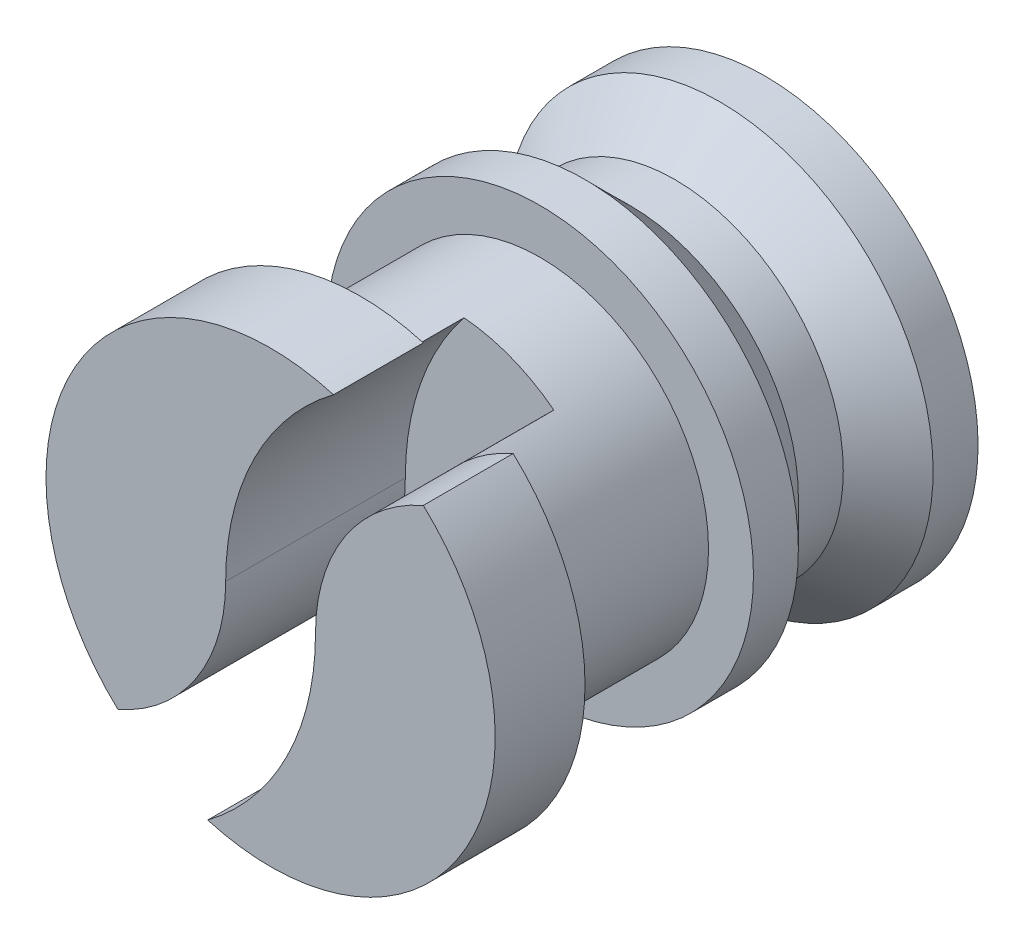
SolidWorks part; units mm, degrees
ref_plane "Спереди" through (0, 0, 0) normal (0, 0, 1) x (1, 0, 0)
ref_plane "Сверху" through (0, 0, 0) normal (0, 1, 0) x (1, 0, 0)
ref_plane "Справа" through (0, 0, 0) normal (1, 0, 0) x (0, 0, -1)
sketch "Эскиз1" plane through (0, 0, 0) normal (0, 0, 1) x (1, 0, 0)
  circle A0 centre (0, 0) radius 7.5
  dimension "D1" = 15
extrude "Бобышка-Вытянуть1" add sketch "Эскиз1" along normal blind 14 and the other way blind 2
sketch "Эскиз2" plane through (0, 0, 0) normal (0, 0, 1) x (1, 0, 0)
  circle A0 centre (0, 0) radius 9.5
  dimension "D1" = 19
extrude "Бобышка-Вытянуть2" add sketch "Эскиз2" along normal blind 2 from offset 2
sketch "Эскиз5" plane through (0, 0, 0) normal (0, 0, 1) x (1, 0, 0)
  circle A0 centre (0, 0) radius 10
  dimension "D1" = 20
extrude "Бобышка-Вытянуть3" add sketch "Эскиз5" along normal blind 4 from offset 12
sketch "Эскиз9" plane through (0, 0, 0) normal (0, 0, 1) x (1, 0, 0)
  line L0 (0, -1000) -> (0, 49000) construction
  line L1 (2, -999.8394) -> (2, 49000.1606) construction
  line L2 (-2, -1000.2983) -> (-2, 48999.7017) construction
  line L3 (-1000, 0) -> (49000, 0) construction
  circle A9 centre (0, 0) radius 15
  arc A10 (9.05, 11.9623) -> (-2, 0) centre (10, 0) ccw
  arc A11 (13.05, 7.3958) -> (2, 0) centre (10, 0) ccw
  arc A12 (-13.05, -7.3958) -> (-2, 0) centre (-10, 0) ccw
  arc A13 (-9.05, -11.9623) -> (2, 0) centre (-10, 0) ccw
  dimension "D1" = 30
  dimension "D5" = 10
  dimension "D2" = 2
  dimension "D3" = 2
extrude "Вырез-Вытянуть3" cut sketch "Эскиз9" along normal blind 8 from offset 8 contours A9 A13 A11 A10 A12 region at (0, 0, 0)
sketch "Эскиз10" plane through (0, 0, 0) normal (0, 0, 1) x (1, 0, 0)
  circle A0 centre (0, 0) radius 6.5
  dimension "D1" = 13
extrude "Вырез-Вытянуть4" cut sketch "Эскиз10" along normal blind 3
sketch "Эскиз11" plane through (0, 0, 0) normal (0, 0, 1) x (1, 0, 0)
  line L1 (-5, -2.5) -> (5, -2.5)
  line L2 (-5, -2.5) -> (-5, 2.5)
  line L3 (-5, 2.5) -> (5, 2.5)
  line L4 (5, -2.5) -> (5, 2.5)
  line L5 (-5, -2.5) -> (5, 2.5) construction
  line L6 (-5, 2.5) -> (5, -2.5) construction
  point P0 (0, 0)
  dimension "D1" = 5
  dimension "D2" = 10
extrude "Вырез-Вытянуть5" cut sketch "Эскиз11" along normal blind 5
sketch "Эскиз12" plane through (0, 0, 0) normal (1, 0, 0) x (0, 0, -1)
  line L0 (-2, 9.5) -> (0, 7.5)
  line L1 (0, 11) -> (0, -11) construction
  line L2 (2, 7.5) -> (-2, 7.5) construction
  line L3 (0, 7.5) -> (-2, 7.5)
  line L4 (-2, -9.5) -> (-2, 9.5) construction
  line L5 (-2, 7.5) -> (-2, 9.5)
  line L6 (0, 0) -> (-6.2922, 0) construction
revolve "Повернуть1" add sketch "Эскиз12" angle 360 about L6
sketch "Эскиз13" plane through (0, 0, 0) normal (1, 0, 0) x (0, 0, -1)
  line L0 (-2, 9.5) -> (7.2712, 9.5) construction
  line L8 (0, 0) -> (-6.5791, 0) construction
  line L11 (2, 7.5) -> (4, 9.5)
  line L13 (4, 9.5) -> (6, 9.5)
  line L14 (6, 9.5) -> (6, 7.5)
  line L15 (6, 7.5) -> (4, 7.5)
  line L16 (4, 7.5) -> (2, 5.5)
  line L17 (2, -7.5) -> (2, 7.5) construction
  line L19 (2, 7.5) -> (2, 5.5)
  dimension "D1" = 2
  dimension "D2" = 2
  dimension "D3" = 2
  dimension "D4" = 2
  dimension "D5" = 2
revolve "Повернуть2" add sketch "Эскиз13" angle 360 about L8
sketch "Эскиз16" plane through (0, 0, 0) normal (1, 0, 0) x (0, 0, -1)
  line L0 (6, 7.5) -> (4, 7.5)
  line L1 (4, 7.5) -> (2, 5.5)
  line L2 (2, 5.5) -> (2, -5.5)
  line L3 (2, -5.5) -> (4, -7.5)
  line L4 (4, -7.5) -> (6, -7.5)
  line L5 (6, -7.5) -> (6, 7.5)
extrude "Бобышка-Вытянуть6" add sketch "Эскиз16" along normal blind 1.5 and the other way blind 1.5
